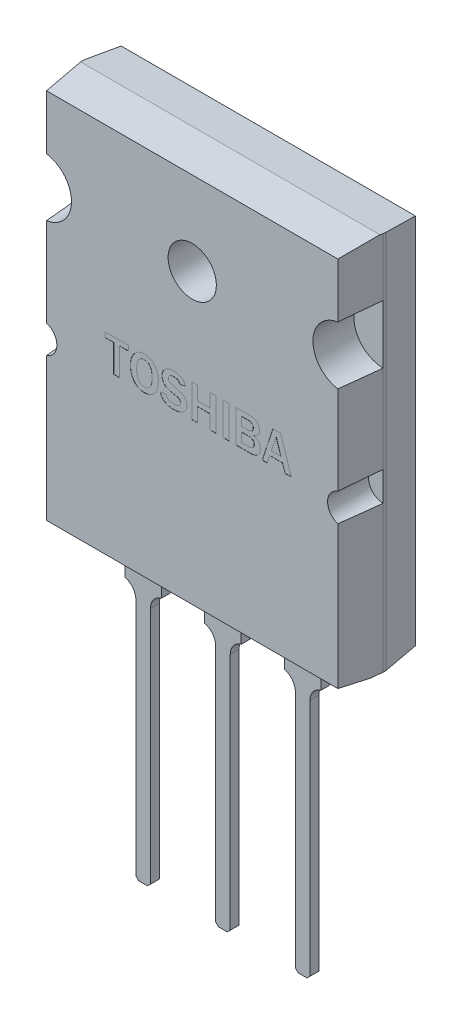
SolidWorks part; units mm, degrees
ref_plane "Płaszczyzna przednia" through (0, 0, 0) normal (0, 0, 1) x (1, 0, 0)
ref_plane "Płaszczyzna górna" through (0, 0, 0) normal (0, 1, 0) x (1, 0, 0)
ref_plane "Płaszczyzna prawa" through (0, 0, 0) normal (1, 0, 0) x (0, 0, -1)
sketch "Szkic1" plane through (0, 0, 0) normal (0, 0, 1) x (1, 0, 0)
  line L0 (-13.1826, 19.7455) -> (-13.1826, -49980.2545) construction
  line L1 (-23.4326, 19.7455) -> (-2.9326, 19.7455)
  line L2 (-23.4326, 19.7455) -> (-23.4326, -6.2545)
  line L3 (-23.4326, -6.2545) -> (-2.9326, -6.2545)
  line L4 (-2.9326, 19.7455) -> (-2.9326, -6.2545)
  circle A0 centre (-13.1826, 13.7455) radius 1.65
  point P6 (-13.1826, 19.7455)
  dimension "D3" = 3.3
  dimension "D1" = 20.5
  dimension "D2" = 26
  dimension "D4" = 6
extrude "Dodanie-wyciągnięcie1" add sketch "Szkic1" along normal blind 5.2
sketch "Szkic2" plane through (0, 0, 5.2) normal (0, 0, 1) x (1, 0, 0)
  line L0 (-23.4326, 19.7455) -> (-23.4326, -6.2545) construction
  line L1 (-13.1826, 19.7455) -> (-13.1826, -49980.2545) construction
  line L2 (-2.9326, 19.7455) -> (-23.4326, 19.7455) construction
  circle A0 centre (-23.4326, 13.7455) radius 2
  circle A1 centre (-2.9326, 13.7455) radius 2
  circle A2 centre (-23.4326, 4.7455) radius 1
  circle A3 centre (-2.9326, 4.7455) radius 1
  point P8 (-13.1826, 19.7455)
  dimension "D1" = 4
  dimension "D2" = 2
  dimension "D3" = 11
extrude "Wytnij-wyciągnięcie1" cut sketch "Szkic2" against normal blind 2.8
sketch "Szkic4" plane through (0, -6.2545, 0) normal (0, -1, 0) x (1, 0, 0)
  line L0 (-13.1826, 5.2) -> (-13.1826, -49994.8) construction
  line L1 (-14.4333, 3.1) -> (-11.9333, 3.1)
  line L2 (-14.4333, 3.1) -> (-14.4333, 2.5)
  line L3 (-14.4333, 2.5) -> (-11.9333, 2.5)
  line L4 (-11.9333, 3.1) -> (-11.9333, 2.5)
  line L5 (-23.4326, 5.2) -> (-2.9326, 5.2) construction
  line L6 (-14.4333, 2.5) -> (-11.9333, 3.1) construction
  line L7 (-11.9333, 2.5) -> (-14.4333, 3.1) construction
  line L8 (-14.4333, 2.8) -> (-11.9333, 2.8) construction
  line L9 (-23.4326, 0) -> (-2.9326, 0) construction
  point P8 (-13.1826, 5.2)
  dimension "D1" = 0.6
  dimension "D2" = 2.5
  dimension "D3" = 2.8
extrude "Dodanie-wyciągnięcie2" add sketch "Szkic4" along normal blind 2.5
sketch "Szkic7" plane through (0, -8.7545, 0) normal (0, -1, 0) x (1, 0, 0)
  line L0 (-11.9333, 3.1) -> (-14.4333, 3.1) construction
  line L1 (-13.6833, 3.1) -> (-12.6833, 3.1)
  line L2 (-13.6833, 3.1) -> (-13.6833, 2.5)
  line L3 (-13.6833, 2.5) -> (-12.6833, 2.5)
  line L4 (-12.6833, 3.1) -> (-12.6833, 2.5)
  line L5 (-13.1833, 3.1) -> (-13.1833, 2.5476) construction
  line L7 (-14.4333, 2.5) -> (-11.9333, 2.5) construction
  line L8 (-13.1833, 2.5) -> (-13.1833, 3.1) construction
  dimension "D1" = 1
extrude "Dodanie-wyciągnięcie3" add sketch "Szkic7" along normal blind 17.5
fillet "Zaokrąglenie2" radius 1 2 edges
chamfer "Sfazowanie1" distance 0.2 angle 45 2 edges at (-12.6833, -26.2545, 2.8) (-13.6833, -26.2545, 2.8)
sketch3d "Szkic 3D1"
  line L0 (-13.1826, -6.2545, 5.2) -> (-13.1826, -6.2545, -49994.8) construction
  line L1 (-23.4326, -6.2545, 5.2) -> (-2.9326, -6.2545, 5.2) construction
  line L2 (-11.9333, -8.7545, 2.5) -> (-11.9333, -6.2545, 2.5) construction
  line L3 (-23.4326, -6.2545, 0) -> (-2.9326, -6.2545, 0) construction
  point P4 (-13.1826, -6.2545, 5.2)
  point P10 (-13.1826, -6.2545, 0)
pattern_linear "Szyk liniowy2" count 2 spacing 5.45 along (-1, 0, 0) count 2 spacing 5.45 along (1, 0, 0) of "Dodanie-wyciągnięcie2", "Dodanie-wyciągnięcie3", "Zaokrąglenie2", "Sfazowanie1"
chamfer "Sfazowanie3" distance 2.2 angle 5 2 edges at (-23.4326, 6.7455, 0) (-2.9326, 6.7455, 0)
chamfer "Sfazowanie4" distance 2.8 angle 6 6 edges at (-2.9326, -1.2545, 5.2) (-2.9326, 8.7455, 5.2) (-2.9326, 17.7455, 5.2) (-23.4326, 17.7455, 5.2) (-23.4326, -1.2545, 5.2) (-23.4326, 8.7455, 5.2)
chamfer "Sfazowanie5" distance 2.8 angle 6 2 edges at (-13.1826, 19.7455, 0) (-13.1826, 19.7455, 5.2)
chamfer "Sfazowanie6" distance 2.2 angle 7 1 edges at (-13.1826, -6.2545, 0)
chamfer "Sfazowanie7" distance 2 angle 8 1 edges at (-13.1826, -6.2545, 5.2)
sketch "Szkic8" plane through (0, 0, 5.2) normal (0, 0, 1) x (1, 0, 0)
  line L0 (-23.1384, 11.7673) -> (-23.1384, 5.7012) construction
  text T0 "TOSHIBA" font "Franklin Gothic Medium" height in points 9
  dimension "D1" = 4
extrude "Wytnij-wyciągnięcie2" cut sketch "Szkic8" against normal blind 0.01
